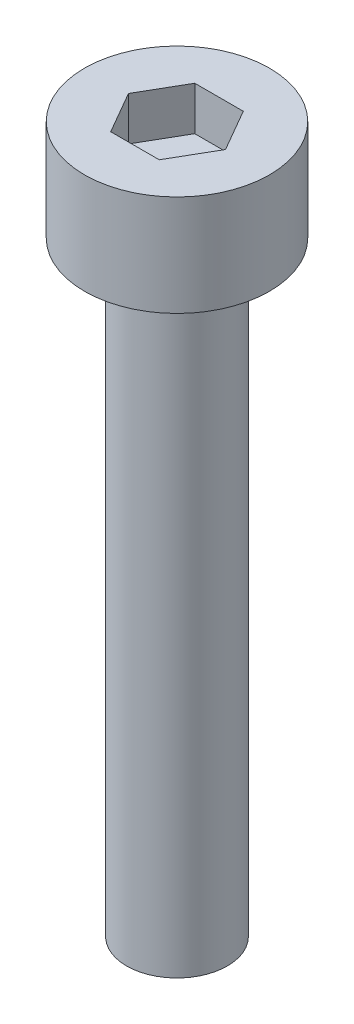
SolidWorks part; units mm, degrees
material "普通碳钢"
ref_plane "前视基准面" through (0, 0, 0) normal (0, 0, 1) x (1, 0, 0)
ref_plane "上视基准面" through (0, 0, 0) normal (0, 1, 0) x (1, 0, 0)
ref_plane "右视基准面" through (0, 0, 0) normal (1, 0, 0) x (0, 0, -1)
sketch "草图1" plane through (0, 0, 0) normal (0, 1, 0) x (1, 0, 0)
  circle A0 centre (0, 0) radius 1.5
  circle A1 centre (0, 0) radius 2.75
  dimension "公称直径" = 3
  dimension "外径" = 5.5
extrude "头部高" add sketch "草图1" along normal blind 3 contours A0 | A1 A0 region at (0, 0, 0) region at (-2.6722, 0, 0)
extrude "公称长度" add sketch "草图1<3>" against normal blind 18 contours A0 region at (0, 0, 0)
sketch "草图1<3>" plane through (0, 0, 0) normal (0, 1, 0) x (1, 0, 0) same geometry as "草图1"
sketch "草图2" plane through (0, 3, 0) normal (0, 1, 0) x (1, 0, 0)
  line L1 (1.4434, 0) -> (0.7217, 1.25)
  line L2 (0.7217, 1.25) -> (-0.7217, 1.25)
  line L3 (-0.7217, 1.25) -> (-1.4434, 0)
  line L4 (-1.4434, 0) -> (-0.7217, -1.25)
  line L5 (-0.7217, -1.25) -> (0.7217, -1.25)
  line L6 (0.7217, -1.25) -> (1.4434, 0)
  circle A0 centre (0, 0) radius 1.25 construction
  dimension "D1" = 2.5
extrude "切除-拉伸1" cut sketch "草图2" against normal blind 1.3
